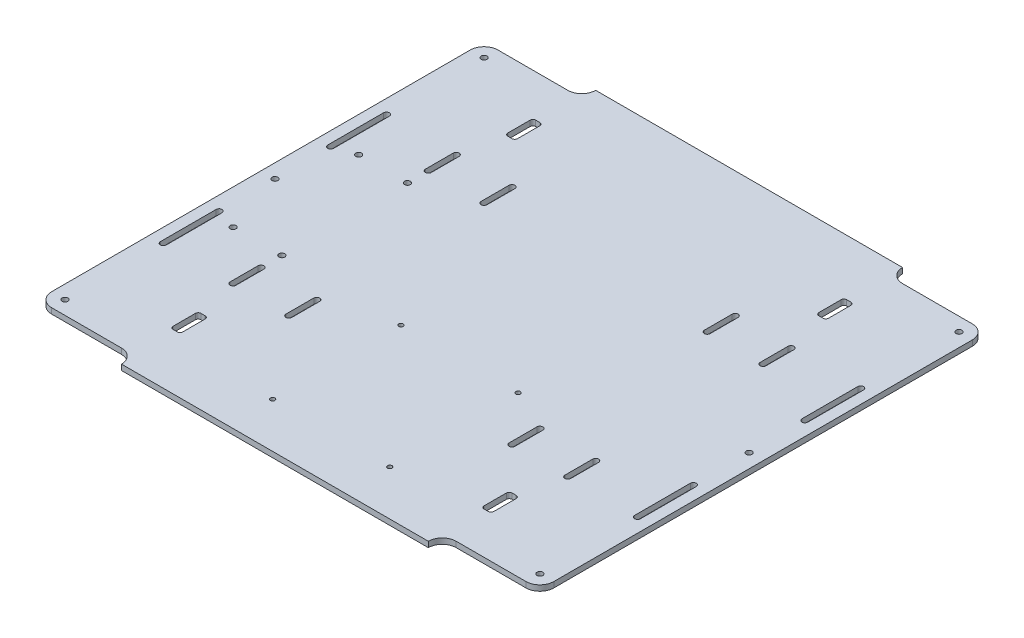
SolidWorks part; units mm, degrees
ref_plane "前视基准面" through (0, 0, 0) normal (0, 0, 1) x (1, 0, 0)
ref_plane "上视基准面" through (0, 0, 0) normal (0, 1, 0) x (1, 0, 0)
ref_plane "右视基准面" through (0, 0, 0) normal (1, 0, 0) x (0, 0, -1)
other "Configuration Table"
sketch "草图1" plane through (0, 0, 0) normal (0, 1, 0) x (1, 0, 0)
  line L1 (-170, -160) -> (170, -160)
  line L2 (-180, -150) -> (-180, 150)
  line L3 (-170, 160) -> (170, 160)
  line L4 (180, -150) -> (180, 150)
  line L5 (-180, -160) -> (-176.8966, -157.2414) construction
  line L6 (-180, 160) -> (-176.8966, 157.2414) construction
  line L8 (176.8966, 157.2414) -> (180, 160) construction
  line L9 (176.8966, -157.2414) -> (180, -160) construction
  arc A0 (170, -160) -> (180, -150) centre (170, -150) ccw
  arc A1 (-180, 150) -> (-170, 160) centre (-170, 150) cw
  arc A2 (-170, -160) -> (-180, -150) centre (-170, -150) cw
  arc A3 (170, 160) -> (180, 150) centre (170, 150) cw
  point P0 (0, 0)
  dimension "D3" = 10
  dimension "D1" = 360
  dimension "D2" = 320
extrude "凸台-拉伸1" add sketch "草图1" along normal mid plane 4
sketch "草图5" plane through (0, 2, 0) normal (0, 1, 0) x (1, 0, 0)
  line L0 (0, 0) -> (0, 142.7283) construction
  line L1 (180, 0) -> (-180, 0) construction
  line L2 (-180, 150) -> (-180, -150) construction
  line L4 (170, 160) -> (-170, 160) construction
  circle A17 centre (80, 80) radius 2.1
  circle A18 centre (120, 80) radius 2.1
  circle A19 centre (-120, 80) radius 2.1
  circle A20 centre (-80, 80) radius 2.1
  circle A23 centre (-80, -80) radius 2.1
  circle A24 centre (-120, -80) radius 2.1
  circle A25 centre (120, -80) radius 2.1
  circle A26 centre (80, -80) radius 2.1
  circle A29 centre (-170, 0) radius 2.1
  circle A30 centre (-170, -40) radius 2.1
  circle A31 centre (-170, -80) radius 2.1
  circle A32 centre (-170, 80) radius 2.1
  circle A33 centre (-170, 40) radius 2.1
  circle A34 centre (170, 40) radius 2.1
  circle A35 centre (170, 80) radius 2.1
  circle A36 centre (170, -80) radius 2.1
  circle A37 centre (170, -40) radius 2.1
  circle A38 centre (170, 0) radius 2.1
  dimension "D2" = 80
  dimension "D1" = 4.2
  dimension "D3" = 10
extrude "切除-拉伸4" cut sketch "草图5" against normal blind 240
sketch "草图6" plane through (0, 2, 0) normal (0, 1, 0) x (1, 0, 0)
  line L0 (170, 160) -> (-170, 160) construction
  line L1 (-180, 150) -> (-180, -150) construction
  line L2 (180, -150) -> (180, 150) construction
  line L3 (-170, -160) -> (170, -160) construction
  circle A0 centre (-170.25, 150.25) radius 2.1
  circle A1 centre (170.25, 150.25) radius 2.1
  circle A2 centre (170.25, -150.25) radius 2.1
  circle A3 centre (-170.25, -150.25) radius 2.1
  dimension "D1" = 4.2
  dimension "D4" = 4.2
  dimension "D6" = 4.2
  dimension "D8" = 4.2
  dimension "D2" = 9.75
  dimension "D3" = 9.75
  dimension "D5" = 9.75
  dimension "D7" = 9.75
  dimension "D9" = 9.75
  dimension "D10" = 9.75
extrude "切除-拉伸5" cut sketch "草图6" against normal blind 10
sketch "草图7" plane through (0, -2, 0) normal (0, -1, 0) x (-1, 0, 0)
  line L0 (180, 150) -> (180, -150) construction
  line L1 (170, -160) -> (-170, -160) construction
  circle A0 centre (145, -110) radius 2.1
  dimension "D1" = 4.2
  dimension "D2" = 35
  dimension "D3" = 50
extrude "切除-拉伸6" cut sketch "草图7" against normal blind 10
sketch "草图8" plane through (0, 2, 0) normal (0, 1, 0) x (1, 0, 0)
  line L25 (-148.8459, -103.0469) -> (-123.0599, -103.0469)
  line L26 (-148.8459, -103.0469) -> (-148.8459, -118.0194)
  line L27 (-148.8459, -118.0194) -> (-123.0599, -118.0194)
  line L28 (-123.0599, -103.0469) -> (-123.0599, -118.0194)
extrude "凸台-拉伸2" add sketch "草图8" against normal blind 6
sketch "草图9" plane through (0, -2, 0) normal (0, -1, 0) x (1, 0, 0)
  line L1 (180, 150) -> (180, -150) construction
  circle A0 centre (50, 137.6322) radius 1.6
  circle A1 centre (50, 45.6322) radius 1.6
  circle A2 centre (-34, 45.6322) radius 1.6
  circle A3 centre (-34, 137.6322) radius 1.6
  dimension "D1" = 3.2
  dimension "D2" = 3.2
  dimension "D3" = 3.2
  dimension "D4" = 3.2
  dimension "D5" = 84
  dimension "D6" = 92
  dimension "D7" = 130
extrude "切除-拉伸7" cut sketch "草图9" against normal blind 10
sketch "草图10" plane through (0, 2, 0) normal (0, 1, 0) x (1, 0, 0)
  line L5 (170, 160) -> (-170, 160) construction
  line L6 (-110, 170) -> (110, 170)
  line L7 (0, 0) -> (-180, 0) construction
  line L8 (-180, 150) -> (-180, -150) construction
  line L13 (-110, 170) -> (-110, 160)
  line L14 (-110, 160) -> (110, 160)
  line L15 (110, 170) -> (110, 160)
  line L16 (-110, 170) -> (110, 160) construction
  line L17 (-110, 160) -> (110, 170) construction
  line L18 (-110, -160) -> (110, -160)
  line L19 (110, -170) -> (110, -160)
  line L20 (-110, -170) -> (110, -170)
  line L21 (-110, -170) -> (-110, -160)
  point P0 (0, 165)
  line M38 (-170, -160) -> (170, -160)
  dimension "D1" = 220
  dimension "D2" = 10
  dimension "D3" = 220
extrude "凸台-拉伸3" add sketch "草图10" against normal blind 4 contours L21 L20 L19 M38 | L15 L14 L13 L6 region at (0, 2, 165)
fillet "圆角1" radius 10 4 edges at (-110, 0, 160) (110, 0, 160) (110, 0, -160) (-110, 0, -160)
sketch "草图13" plane through (0, -2, 0) normal (0, -1, 0) x (1, 0, 0)
  line L0 (-180, -150) -> (-180, 150) construction
  line L1 (0, 0) -> (-180, 0) construction
  circle A0 centre (-155, 45) radius 2.1
  circle A1 centre (-120, 45) radius 2.1
  circle A2 centre (-120, -45) radius 2.1
  circle A3 centre (-155, -45) radius 2.1
  dimension "D1" = 4.2
  dimension "D3" = 4.2
  dimension "D4" = 35
  dimension "D5" = 90
  dimension "D2" = 25
extrude "切除-拉伸8" cut sketch "草图13" against normal blind 10
sketch "草图14" plane through (0, -2, 0) normal (0, -1, 0) x (1, 0, 0)
  line L0 (-170, 160) -> (-120, 160) construction
  line L1 (-180, -150) -> (-180, 150) construction
  line L2 (-120, 100) -> (-120, 140) construction
  line L3 (-115, 112) -> (-115, 128)
  line L4 (-113, 130) -> (-110, 130)
  line L5 (-108, 128) -> (-108, 112)
  line L6 (-110, 110) -> (-113, 110)
  line L7 (0, 0) -> (-180, 0) construction
  line L8 (0, 0) -> (0, 170) construction
  line L9 (-110, 170) -> (110, 170) construction
  line L10 (108, 128) -> (108, 112)
  line L11 (113, 130) -> (110, 130)
  line L12 (115, 112) -> (115, 128)
  line L13 (110, 110) -> (113, 110)
  line L14 (113, -130) -> (110, -130)
  line L15 (115, -112) -> (115, -128)
  line L16 (110, -110) -> (113, -110)
  line L17 (108, -128) -> (108, -112)
  line L18 (-108, -128) -> (-108, -112)
  line L19 (-113, -130) -> (-110, -130)
  line L20 (-115, -112) -> (-115, -128)
  line L21 (-110, -110) -> (-113, -110)
  arc A0 (-108, 112) -> (-110, 110) centre (-110, 112) cw
  arc A1 (-110, 130) -> (-108, 128) centre (-110, 128) cw
  arc A2 (-113, 110) -> (-115, 112) centre (-113, 112) cw
  arc A3 (-115, 128) -> (-113, 130) centre (-113, 128) cw
  arc A4 (110, -110) -> (108, -112) centre (110, -112) ccw
  arc A5 (115, -112) -> (113, -110) centre (113, -112) ccw
  arc A6 (110, -130) -> (108, -128) centre (110, -128) cw
  arc A7 (113, -130) -> (115, -128) centre (113, -128) ccw
  arc A8 (-115, -112) -> (-113, -110) centre (-113, -112) cw
  arc A9 (-113, -130) -> (-115, -128) centre (-113, -128) cw
  arc A10 (-108, -112) -> (-110, -110) centre (-110, -112) ccw
  arc A11 (-108, -128) -> (-110, -130) centre (-110, -128) cw
  arc A12 (115, 112) -> (113, 110) centre (113, 112) cw
  arc A13 (113, 130) -> (115, 128) centre (113, 128) cw
  arc A14 (108, 112) -> (110, 110) centre (110, 112) ccw
  arc A15 (108, 128) -> (110, 130) centre (110, 128) cw
  point P0 (-120, 100)
  point P11 (-120, 120)
  point P12 (-115, 120)
  point P33 (-108, 110)
  point P36 (-108, 130)
  point P39 (-115, 110)
  point P42 (-115, 130)
  point P45 (108, -110)
  point P48 (115, -110)
  point P51 (108, -130)
  point P54 (115, -130)
  point P57 (-115, -110)
  point P60 (-115, -130)
  point P63 (-108, -110)
  point P66 (-108, -130)
  point P69 (115, 110)
  point P72 (115, 130)
  point P75 (108, 110)
  point P78 (108, 130)
  dimension "D7" = 2
  dimension "D8" = 2
  dimension "D1" = 60
  dimension "D2" = 60
  dimension "D3" = 40
  dimension "D4" = 20
  dimension "D5" = 7
  dimension "D6" = 5
extrude "切除-拉伸9" cut sketch "草图14" against normal blind 10
sketch "草图15" plane through (0, 2, 0) normal (0, 1, 0) x (1, 0, 0)
  line L0 (0, 0) -> (180, 0) construction
  line L3 (180, -150) -> (180, 150) construction
  line L5 (0, 0) -> (0, 170) construction
  line L6 (-110, 170) -> (110, 170) construction
  line L7 (-120, 80) -> (-120, 60) construction
  line L16 (-117.9, 80) -> (-117.9, 60)
  line L25 (-122.1, 80) -> (-122.1, 60)
  line L30 (-80, 80) -> (-80, 60) construction
  line L33 (-77.9, 80) -> (-77.9, 60)
  line L36 (-82.1, 80) -> (-82.1, 60)
  line L39 (80, 80) -> (80, 60) construction
  line L42 (77.9, 80) -> (77.9, 60)
  line L45 (170, 80) -> (170, 40) construction
  line L46 (172.1, 80) -> (172.1, 40)
  line L47 (167.9, 80) -> (167.9, 40)
  line L48 (170, -80) -> (170, -40) construction
  line L49 (172.1, -80) -> (172.1, -40)
  line L50 (167.9, -80) -> (167.9, -40)
  line L51 (-170, -80) -> (-170, -40) construction
  line L52 (-172.1, -80) -> (-172.1, -40)
  line L53 (-167.9, -80) -> (-167.9, -40)
  line L54 (-170, 80) -> (-170, 40) construction
  line L55 (-172.1, 80) -> (-172.1, 40)
  line L56 (-167.9, 80) -> (-167.9, 40)
  line L57 (82.1, 80) -> (82.1, 60)
  line L58 (120, 80) -> (120, 60) construction
  line L59 (117.9, 80) -> (117.9, 60)
  line L60 (122.1, 80) -> (122.1, 60)
  line L61 (120, -80) -> (120, -60) construction
  line L62 (117.9, -80) -> (117.9, -60)
  line L63 (122.1, -80) -> (122.1, -60)
  line L64 (80, -80) -> (80, -60) construction
  line L65 (77.9, -80) -> (77.9, -60)
  line L66 (82.1, -80) -> (82.1, -60)
  line L67 (-80, -80) -> (-80, -60) construction
  line L68 (-77.9, -80) -> (-77.9, -60)
  line L69 (-82.1, -80) -> (-82.1, -60)
  line L70 (-120, -80) -> (-120, -60) construction
  line L71 (-117.9, -80) -> (-117.9, -60)
  line L72 (-122.1, -80) -> (-122.1, -60)
  arc A32 (172.1, 80) -> (167.9, 80) centre (170, 80) ccw
  arc A33 (167.9, 40) -> (172.1, 40) centre (170, 40) ccw
  arc A34 (172.1, -80) -> (167.9, -80) centre (170, -80) cw
  arc A35 (167.9, -40) -> (172.1, -40) centre (170, -40) cw
  arc A36 (-172.1, -80) -> (-167.9, -80) centre (-170, -80) ccw
  arc A37 (-167.9, -40) -> (-172.1, -40) centre (-170, -40) ccw
  arc A38 (-172.1, 80) -> (-167.9, 80) centre (-170, 80) cw
  arc A39 (-167.9, 40) -> (-172.1, 40) centre (-170, 40) cw
  arc A40 (-117.9, 80) -> (-122.1, 80) centre (-120, 80) ccw
  arc A41 (-122.1, 60) -> (-117.9, 60) centre (-120, 60) ccw
  arc A42 (-77.9, 80) -> (-82.1, 80) centre (-80, 80) ccw
  arc A43 (-82.1, 60) -> (-77.9, 60) centre (-80, 60) ccw
  arc A44 (77.9, 80) -> (82.1, 80) centre (80, 80) cw
  arc A45 (82.1, 60) -> (77.9, 60) centre (80, 60) cw
  arc A46 (117.9, 80) -> (122.1, 80) centre (120, 80) cw
  arc A47 (122.1, 60) -> (117.9, 60) centre (120, 60) cw
  arc A48 (117.9, -80) -> (122.1, -80) centre (120, -80) ccw
  arc A49 (122.1, -60) -> (117.9, -60) centre (120, -60) ccw
  arc A50 (77.9, -80) -> (82.1, -80) centre (80, -80) ccw
  arc A51 (82.1, -60) -> (77.9, -60) centre (80, -60) ccw
  arc A52 (-77.9, -80) -> (-82.1, -80) centre (-80, -80) cw
  arc A53 (-82.1, -60) -> (-77.9, -60) centre (-80, -60) cw
  arc A54 (-117.9, -80) -> (-122.1, -80) centre (-120, -80) cw
  arc A55 (-122.1, -60) -> (-117.9, -60) centre (-120, -60) cw
  point P2 (-120, 80)
  point P7 (-120, 70)
  point P21 (-80, 70)
  point P28 (80, 70)
  point P35 (120, 70)
  point P42 (120, -70)
  point P49 (80, -70)
  point P56 (-80, -70)
  point P63 (-120, -70)
  point P74 (170, 60)
  point P81 (170, -60)
  point P88 (-170, -60)
  point P95 (-170, 60)
  dimension "D1" = 2.1
  dimension "D2" = 20
  dimension "D3" = 2.1
  dimension "D5" = 2.1
  dimension "D4" = 90
extrude "切除-拉伸10" cut sketch "草图15" against normal blind 10
equation "\"2.1、\"=2.62227"
